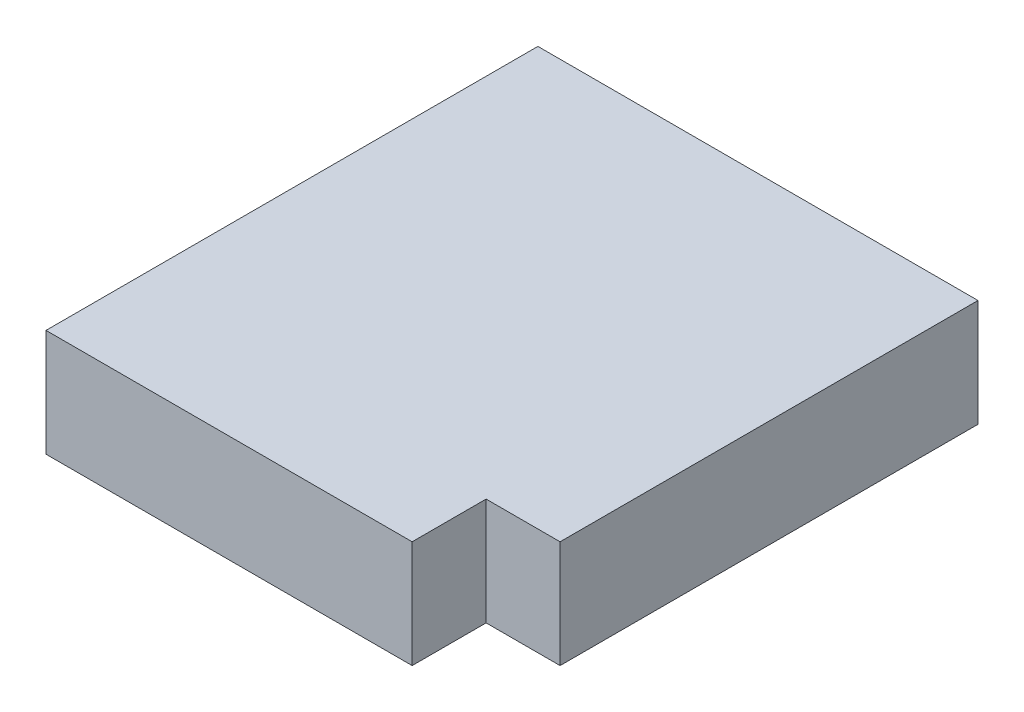
SolidWorks part; units mm, degrees
ref_plane "Front Plane" through (0, 0, 0) normal (0, 0, 1) x (1, 0, 0)
ref_plane "Top Plane" through (0, 0, 0) normal (0, 1, 0) x (1, 0, 0)
ref_plane "Right Plane" through (0, 0, 0) normal (1, 0, 0) x (0, 0, -1)
sketch "Sketch1" plane through (0, 0, 0) normal (0, 1, 0) x (1, 0, 0)
  line L0 (0, 0) -> (29.75, 0)
  line L1 (29.75, 0) -> (29.75, 33.25)
  line L2 (29.75, 33.25) -> (0, 33.25)
  line L3 (0, 33.25) -> (0, 0)
  dimension "D1" = 33.25
  dimension "D2" = 29.75
extrude "Boss-Extrude1" add sketch "Sketch1" along normal blind 7.25
sketch "Sketch2" plane through (0, 7.25, 0) normal (0, 1, 0) x (1, 0, 0)
  line L0 (29.75, 5) -> (24.75, 5)
  line L1 (29.75, 0) -> (29.75, 33.25) construction
  line L2 (24.75, 5) -> (24.75, 0)
  line L3 (0, 0) -> (29.75, 0) construction
  line L4 (24.75, 0) -> (29.75, 0)
  line L5 (29.75, 0) -> (29.75, 5)
  dimension "D1" = 5
  dimension "D2" = 5
extrude "Cut-Extrude1" cut sketch "Sketch2" against normal blind 10
